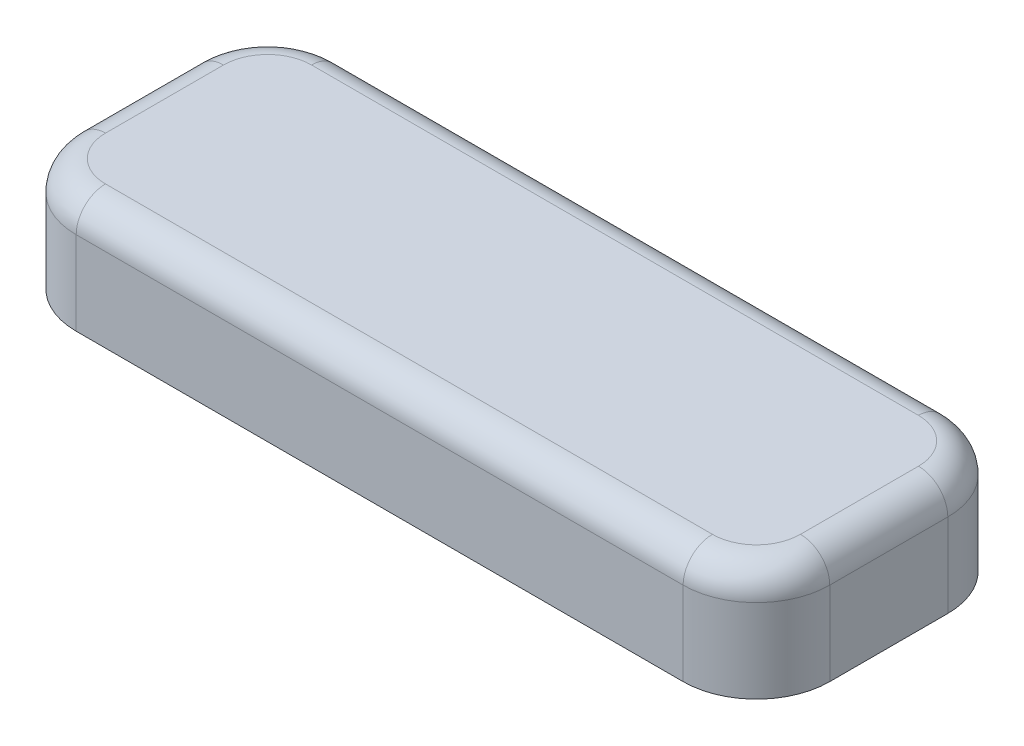
SolidWorks part; units mm, degrees
ref_plane "前视基准面" through (0, 0, 0) normal (0, 0, 1) x (1, 0, 0)
ref_plane "上视基准面" through (0, 0, 0) normal (0, 1, 0) x (1, 0, 0)
ref_plane "右视基准面" through (0, 0, 0) normal (1, 0, 0) x (0, 0, -1)
other "Configuration Table"
sketch "草图1" plane through (0, 0, 0) normal (0, 1, 0) x (1, 0, 0)
  line L0 (-2.2, 0) -> (2.2, 0) construction
  line L1 (0, 2.2) -> (0, -2.2) construction
  line L2 (2.2, 0.6) -> (2.2, -0.6)
  line L3 (-0.6, 2.2) -> (0.6, 2.2)
  line L4 (-2.2, -0.6) -> (-2.2, 0.6)
  line L5 (-0.6, -2.2) -> (0.6, -2.2)
  line L6 (-0.6, 2.2) -> (-0.6, 0.6)
  line L7 (-0.6, 0.6) -> (-2.2, 0.6)
  line L8 (-2.2, -0.6) -> (-0.6, -0.6)
  line L9 (-0.6, -0.6) -> (-0.6, -2.2)
  line L10 (0.6, -2.2) -> (0.6, -0.6)
  line L11 (0.6, -0.6) -> (2.2, -0.6)
  line L12 (2.2, 0.6) -> (0.6, 0.6)
  line L13 (0.6, 0.6) -> (0.6, 2.2)
  line L14 (-11.9062, 0) -> (11.9062, 0) construction
  line L15 (-14.1063, 0) -> (-9.7062, 0) construction
  line L16 (-11.9062, 2.2) -> (-11.9062, -2.2) construction
  line L17 (-14.1063, -0.6) -> (-14.1063, 0.6)
  line L18 (-12.5062, -2.2) -> (-11.3063, -2.2)
  line L19 (-11.3063, 2.2) -> (-12.5062, 2.2)
  line L20 (-9.7062, -0.6) -> (-9.7062, 0.6)
  line L21 (-14.1063, -0.6) -> (-12.5062, -0.6)
  line L22 (-12.5062, -0.6) -> (-12.5062, -2.2)
  line L23 (-11.3063, -2.2) -> (-11.3063, -0.6)
  line L24 (-11.3063, -0.6) -> (-9.7062, -0.6)
  line L25 (-9.7062, 0.6) -> (-11.3063, 0.6)
  line L26 (-11.3063, 0.6) -> (-11.3063, 2.2)
  line L27 (-12.5062, 2.2) -> (-12.5062, 0.6)
  line L28 (-12.5062, 0.6) -> (-14.1063, 0.6)
  line L29 (9.7062, 0) -> (14.1063, 0) construction
  line L30 (11.9062, -2.2) -> (11.9062, 2.2) construction
  line L31 (9.7062, 0.6) -> (9.7062, -0.6)
  line L32 (11.3063, 2.2) -> (12.5062, 2.2)
  line L33 (14.1063, -0.6) -> (14.1063, 0.6)
  line L34 (11.3063, -2.2) -> (12.5062, -2.2)
  line L35 (9.7062, 0.6) -> (11.3063, 0.6)
  line L36 (11.3063, 0.6) -> (11.3063, 2.2)
  line L37 (12.5062, 2.2) -> (12.5062, 0.6)
  line L38 (12.5062, 0.6) -> (14.1063, 0.6)
  line L39 (14.1063, -0.6) -> (12.5062, -0.6)
  line L40 (12.5062, -0.6) -> (12.5062, -2.2)
  line L41 (11.3063, -2.2) -> (11.3063, -0.6)
  line L42 (11.3063, -0.6) -> (9.7062, -0.6)
  circle A0 centre (0, 0) radius 2.8
  circle A1 centre (-11.9062, 0) radius 2.8
  circle A2 centre (11.9062, 0) radius 2.8
  point P4 (0, 0)
  point P7 (0, 0)
  point P10 (2.2, 0)
  point P13 (0, 2.2)
  point P16 (-2.2, 0)
  point P19 (0, -2.2)
  point P28 (0, 0)
  point P31 (-11.9062, 0)
  point P34 (-11.9062, 0)
  point P37 (-14.1063, 0)
  point P40 (-11.9062, -2.2)
  point P43 (-11.9062, 2.2)
  point P46 (-9.7062, 0)
  point P54 (11.9062, 0)
  point P57 (11.9062, 0)
  point P60 (9.7062, 0)
  point P63 (11.9062, 2.2)
  point P66 (14.1063, 0)
  point P69 (11.9062, -2.2)
  dimension "D7" = 5.6
  dimension "D15" = 5.6
  dimension "D22" = 5.6
  dimension "D1" = 4.4
  dimension "D2" = 4.4
  dimension "D3" = 1.2
  dimension "D4" = 1.2
  dimension "D5" = 1.2
  dimension "D6" = 1.2
  dimension "D8" = 23.8125
  dimension "D9" = 4.4
  dimension "D10" = 4.4
  dimension "D11" = 1.2
  dimension "D12" = 1.2
  dimension "D13" = 1.2
  dimension "D14" = 1.2
  dimension "D16" = 4.4
  dimension "D17" = 4.4
  dimension "D18" = 1.2
  dimension "D19" = 1.2
  dimension "D20" = 1.2
  dimension "D21" = 1.2
extrude "凸台-拉伸1" add sketch "草图1" against normal blind 5.5 contours A0 | L8 L9 L5 L10 L11 L2 L12 L13 L3 L6 L7 L4
sketch "草图2" plane through (0, 0, 0) normal (0, 1, 0) x (1, 0, 0)
  line L0 (0, -9.025) -> (0, 9.025) construction
  line L1 (-25.6938, 9.025) -> (25.6938, 9.025)
  line L2 (-25.6938, -9.025) -> (25.6938, -9.025)
  line L3 (-25.6938, 9.025) -> (-25.6938, -9.025)
  line L4 (25.6938, 9.025) -> (25.6938, -9.025)
  point P4 (0, 0)
  point P8 (0, 9.025)
  point P11 (0, -9.025)
  dimension "D1" = 18.05
  dimension "D2" = 51.3875
extrude "凸台-拉伸2" add sketch "草图2" along normal blind 1.2
sketch "草图3" plane through (0, 0, 0) normal (0, 1, 0) x (1, 0, 0)
  line L4 (25.6938, -9.025) -> (25.6938, 9.025)
  line L5 (-25.6938, -9.025) -> (25.6938, -9.025)
  line L6 (-25.6938, 9.025) -> (-25.6938, -9.025)
  line L7 (25.6938, 9.025) -> (-25.6938, 9.025)
  line L8 (25.6938, -9.025) -> (25.6938, 9.025)
  line L9 (-25.6938, -9.025) -> (25.6938, -9.025)
  line L10 (-25.6938, 9.025) -> (-25.6938, -9.025)
  line L11 (25.6938, 9.025) -> (-25.6938, 9.025)
  line L20 (24.4938, -7.825) -> (24.4938, 7.825)
  line L21 (24.4938, 7.825) -> (-24.4938, 7.825)
  line L22 (-24.4938, 7.825) -> (-24.4938, -7.825)
  line L23 (-24.4938, -7.825) -> (24.4938, -7.825)
  line L24 (24.4938, -7.825) -> (24.4938, 7.825)
  line L25 (24.4938, 7.825) -> (-24.4938, 7.825)
  line L26 (-24.4938, 7.825) -> (-24.4938, -7.825)
  line L27 (-24.4938, -7.825) -> (24.4938, -7.825)
  dimension "D1" = 0
  dimension "D2" = 1.2
extrude "凸台-拉伸3" add sketch "草图3" against normal blind 6.5
fillet "圆角1" radius 5 8 edges at (-25.6938, -2.65, -9.025) (25.6938, -2.65, -9.025) (25.6938, -2.65, 9.025) (-25.6938, -2.65, 9.025) (-24.4938, -3.25, -7.825) (24.4938, -3.25, -7.825) (24.4938, -3.25, 7.825) (-24.4938, -3.25, 7.825)
fillet "圆角2" radius 2 16 edges at (24.4938, 0, 0) (0, 0, 7.825) (0, 0, -7.825) (-24.4938, 0, 0) (24.2293, 1.2, -7.5605) (25.6938, 1.2, 0) (24.2293, 1.2, 7.5605) (0, 1.2, 9.025) (-24.2293, 1.2, 7.5605) (-25.6938, 1.2, 0) (-24.2293, 1.2, -7.5605) (0, 1.2, -9.025) (23.0293, 0, 6.3605) (23.0293, 0, -6.3605) (-23.0293, 0, -6.3605) (-23.0293, 0, 6.3605)
extrude "凸台-拉伸4" add sketch "草图1<3>" against normal blind 5.5 contours A2 | L42 L31 L35 L36 L32 L37 L38 L33 L39 L40 L34 L41
sketch "草图1<3>" plane through (0, 0, 0) normal (0, 1, 0) x (1, 0, 0) same geometry as "草图1"
extrude "凸台-拉伸5" add sketch "草图1<4>" against normal blind 5.5 contours A1 | L18 L23 L24 L20 L25 L26 L19 L27 L28 L17 L21 L22
sketch "草图1<4>" plane through (0, 0, 0) normal (0, 1, 0) x (1, 0, 0) same geometry as "草图1"
chamfer "倒角3" distance 0.5 angle 45 3 edges at (-11.9062, 0, 2.8) (0, 0, 2.8) (11.9062, 0, 2.8)
